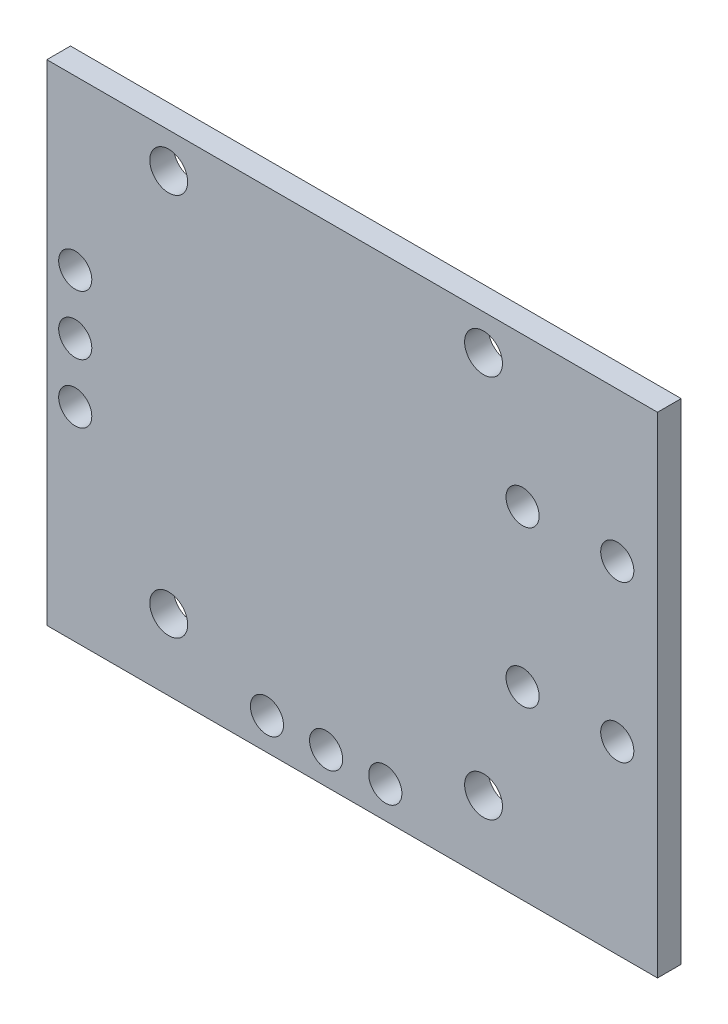
SolidWorks part; units mm, degrees
ref_plane "正面" through (0, 0, 0) normal (0, 0, 1) x (1, 0, 0)
ref_plane "平面" through (0, 0, 0) normal (0, 1, 0) x (1, 0, 0)
ref_plane "右側面" through (0, 0, 0) normal (1, 0, 0) x (0, 0, -1)
sketch "ｽｹｯﾁ1" plane through (0, 0, 0) normal (0, 0, 1) x (1, 0, 0)
  line L0 (0, -9.6) -> (25.8, -9.6) construction
  line L1 (0, 0) -> (25.8, 0)
  line L2 (0, 0) -> (0, -20.7)
  line L3 (0, -20.7) -> (25.8, -20.7)
  line L4 (25.8, 0) -> (25.8, -20.7)
  line L5 (1.2, -20.7) -> (1.2, 0) construction
  line L6 (25.8, -1.5) -> (0, -1.5) construction
  line L7 (20.1, -6.3) -> (24.1, -6.3) construction
  line L8 (20.1, -6.3) -> (20.1, -12.9) construction
  line L9 (20.1, -12.9) -> (24.1, -12.9) construction
  line L10 (24.1, -6.3) -> (24.1, -12.9) construction
  line L11 (25.8, -17.7) -> (0, -17.7) construction
  line L12 (18.45, -20.7) -> (18.45, 0) construction
  line L13 (5.15, 0) -> (5.15, -20.7) construction
  line L14 (25.8, -12.1) -> (0, -12.1) construction
  line L15 (25.8, -7.1) -> (0, -7.1) construction
  line L16 (9.3, -19.35) -> (25.8, -19.35) construction
  line L17 (5.15, -1.5) -> (18.45, -17.7) construction
  line L18 (5.15, -17.7) -> (18.45, -1.5) construction
  line L19 (11.8, -9.6) -> (11.8, -20.7) construction
  line L21 (11.8, -9.6) -> (0, -9.6) construction
  circle A0 centre (1.2, -7.1) radius 0.7
  circle A1 centre (1.2, -9.6) radius 0.7
  circle A2 centre (1.2, -12.1) radius 0.7
  circle A3 centre (5.15, -17.7) radius 0.8
  circle A4 centre (5.15, -1.5) radius 0.8
  circle A5 centre (18.45, -1.5) radius 0.8
  circle A6 centre (18.45, -17.7) radius 0.8
  circle A7 centre (9.3, -19.35) radius 0.7
  circle A8 centre (11.8, -19.35) radius 0.7
  circle A10 centre (20.1, -6.3) radius 0.7
  circle A11 centre (24.1, -6.3) radius 0.7
  circle A12 centre (20.1, -12.9) radius 0.7
  circle A13 centre (24.1, -12.9) radius 0.7
  circle A14 centre (14.3, -19.35) radius 0.7
  dimension "D3" = 1.4
  dimension "D4" = 1.4
  dimension "D8" = 1.6
  dimension "D16" = 1.4
  dimension "D1" = 20.7
  dimension "D2" = 25.8
  dimension "D5" = 6.6
  dimension "D6" = 4
  dimension "D7" = 20.1
  dimension "D9" = 2.5
  dimension "D10" = 1.2
  dimension "D11" = 13.3
  dimension "D12" = 1.35
  dimension "D13" = 3
  dimension "D14" = 2.5
  dimension "D17" = 1.5
  dimension "D18" = 5.15
  dimension "D19" = 2.5
extrude "ﾎﾞｽ - 押し出し1" add sketch "ｽｹｯﾁ1" along normal blind 1 contours L4 L1 L2 L3 A13 A12 A11 A10 A8 A7 A6 A5 A4 A3 A2 A1 A0 region at (12.9221, -10.2962, 0)
